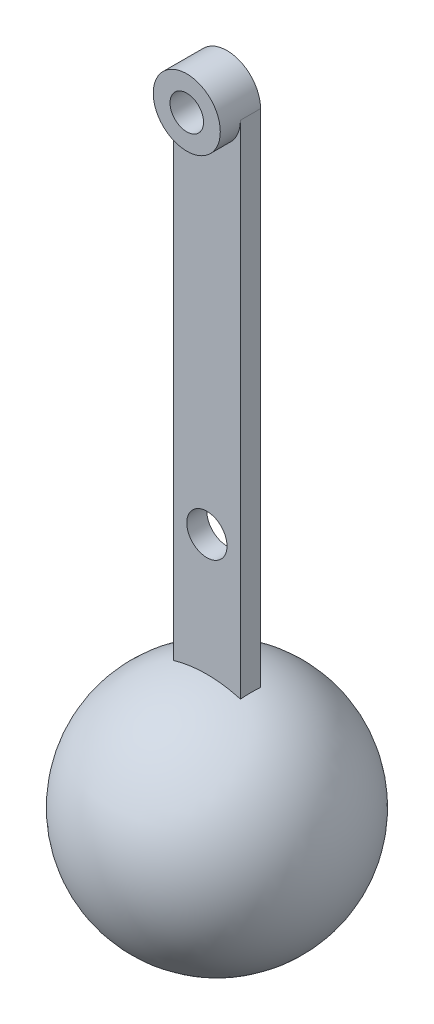
SolidWorks part; units mm, degrees
ref_plane "Front Plane" through (0, 0, 0) normal (0, 0, 1) x (1, 0, 0)
ref_plane "Top Plane" through (0, 0, 0) normal (0, 1, 0) x (1, 0, 0)
ref_plane "Right Plane" through (0, 0, 0) normal (1, 0, 0) x (0, 0, -1)
sketch "Sketch1" plane through (0, 0, 0) normal (0, 0, 1) x (1, 0, 0)
  line L0 (0, 13.4863) -> (0, -12.6942) construction
  line L1 (0, 9) -> (0, -9)
  arc A0 (0, 9) -> (0, -9) centre (0, 0) ccw
  dimension "D1" = 18
revolve "Revolve1" add sketch "Sketch1" angle 360 about L1
sketch "Sketch2" plane through (0, 0, 0) normal (0, 0, 1) x (1, 0, 0)
  line L0 (2.5, 46) -> (2.5, 8.6458)
  line L1 (-2.5, 46) -> (-2.5, 8.6458)
  line L2 (2.5, 8.6458) -> (2.5, 6.9741)
  line L3 (2.5, 6.9741) -> (-2.5, 6.9741)
  line L4 (-2.5, 6.9741) -> (-2.5, 8.6458)
  circle A1 centre (0, 46) radius 2.5
  circle A2 centre (0, 46) radius 1.25
  circle A3 centre (0, 18) radius 1.5
  circle A4 centre (0, 0) radius 9 construction
  point P2 (-2.5, 8.6458)
  point P15 (0, 0)
  point P16 (-2.5, 8.6458)
  point P17 (-2.5, 8.6458)
  point P18 (-2.5, 3.6739)
  point P19 (2.5, 6.9741)
  dimension "D1" = 5
  dimension "D3" = 2.5
  dimension "D4" = 3
  dimension "D6" = 5
  dimension "D2" = 46
  dimension "D5" = 28
extrude "Boss-Extrude1" add sketch "Sketch2" along normal mid plane 1.5 contours L1 L0 A1 A3 region at (0, 25.8073, 0)
extrude "Boss-Extrude2" add sketch "Sketch2<3>" against normal blind 0.75 and the other way blind 2.25 contours A1 A2 region at (0, 43.5707, 0)
sketch "Sketch2<3>" plane through (0, 0, 0) normal (0, 0, 1) x (1, 0, 0) same geometry as "Sketch2"
